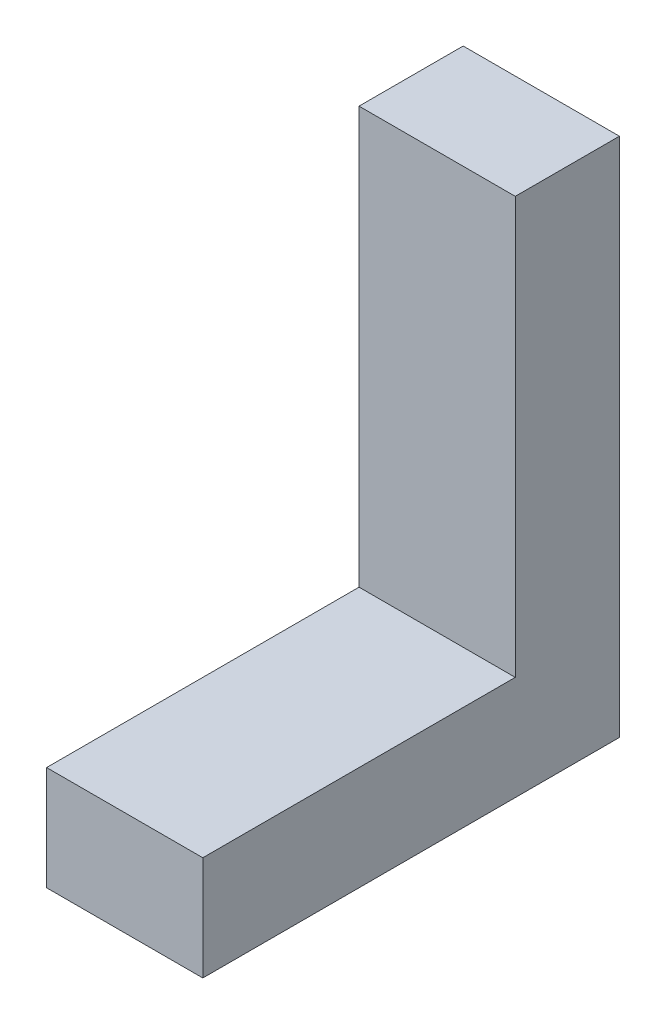
SolidWorks part; units mm, degrees
ref_plane "前视基准面" through (0, 0, 0) normal (0, 0, 1) x (1, 0, 0)
ref_plane "上视基准面" through (0, 0, 0) normal (0, 1, 0) x (1, 0, 0)
ref_plane "右视基准面" through (0, 0, 0) normal (1, 0, 0) x (0, 0, -1)
other "Configuration Table"
sketch "Sketch1" plane through (0, 0, 0) normal (1, 0, 0) x (0, 0, -1)
  line L0 (0, 0) -> (-40, 0)
  line L1 (-40, 0) -> (-40, 10)
  line L2 (-40, 10) -> (-10, 10)
  line L3 (-10, 10) -> (-10, 50)
  line L4 (-10, 50) -> (0, 50)
  line L5 (0, 50) -> (0, 0)
extrude "Boss-Extrude1" add sketch "Sketch1" along normal blind 15
sketch3d "3DSketch1"
  line L0 (5, 0, 7.5) -> (5, 100, 7.5) construction
ref_axis "Axis_Slide" through (5, 0, 7.5) along (0, 1, 0)
ref_plane "Mate_Bottom" through (0, 0, 0) normal (1, 0, 0) x (0, 0, -1)
